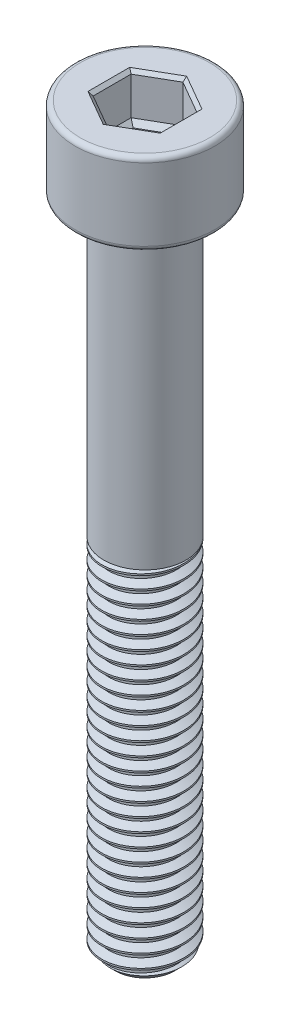
SolidWorks part; units mm, degrees
material "AISI Type A2 Tool Steel"
ref_plane "Front Plane" through (0, 0, 0) normal (0, 0, 1) x (1, 0, 0)
ref_plane "Top Plane" through (0, 0, 0) normal (0, 1, 0) x (1, 0, 0)
ref_plane "Right Plane" through (0, 0, 0) normal (1, 0, 0) x (0, 0, -1)
sketch "Sketch1" plane through (0, 0, 0) normal (0, 1, 0) x (1, 0, 0)
  circle A0 centre (0, 0) radius 2.5
  dimension "D1" = 5
extrude "Boss-Extrude1" add sketch "Sketch1" along normal blind 22
thread "Thread1" pitch 0.8 method cut profile "Thread Profile1" start angle 0, offset 1, length 0, pitch 0.8, diameter 5
ref_plane "Plane1" through (-2.5, 23, 0) normal (0, 0, 1) x (-1, 0, 0)
sketch "Thread Profile1" plane through (-2.5, 23, 0) normal (0, 0, 1) x (-1, 0, 0)
  line L0 (0, 0) -> (0, 0.8) construction
  line L11 (0, 0) -> (0, 0.7)
  line L12 (0, 0.7) -> (-0.433, 0.45)
  line L13 (-0.433, 0.45) -> (-0.433, 0.25)
  line L15 (-0.433, 0.25) -> (0, 0)
  line L17 (-0.433, 0.35) -> (0, 0.35) construction
  point P2 (0, 0)
  dimension "Pitch" = 0.8
  dimension "Profile_Angle" = 60
  dimension "Profile_Land" = 0.2
  dimension "Profile_Height" = 0.433
sketch "Sketch2" plane through (0, 22, 0) normal (0, 1, 0) x (1, 0, 0)
  circle A0 centre (0, 0) radius 2.5
  dimension "D1" = 5
extrude "Boss-Extrude2" add sketch "Sketch2" along normal blind 18
sketch "Sketch3" plane through (0, 40, 0) normal (0, 1, 0) x (1, 0, 0)
  circle A0 centre (0, 0) radius 4.25
  dimension "D1" = 8.5
extrude "Boss-Extrude3" add sketch "Sketch3" along normal blind 5
fillet "Fillet1" radius 0.3 2 edges at (0, 40, 4.25) (0, 45, 4.25)
sketch "Sketch4" plane through (0, 0, 0) normal (0, 0, 1) x (1, 0, 0)
  line L0 (0, 0) -> (0, 0.4416) construction
  line L1 (0, 0) -> (2.51, 0) construction
  line L2 (2.51, 0) -> (2.51, 0.7)
  line L3 (2.51, 0.7) -> (1.81, 0)
  line L4 (1.81, 0) -> (2.51, 0)
  dimension "D1" = 0.7
  dimension "D2" = 45
  dimension "D3" = 2.51
revolve "Cut-Revolve1" cut sketch "Sketch4" angle 360 about L0
sketch "Sketch5" plane through (0, 45, 0) normal (0, 1, 0) x (1, 0, 0)
  line L1 (0, 2.3094) -> (-2, 1.1547)
  line L2 (-2, 1.1547) -> (-2, -1.1547)
  line L3 (-2, -1.1547) -> (0, -2.3094)
  line L4 (0, -2.3094) -> (2, -1.1547)
  line L5 (2, -1.1547) -> (2, 1.1547)
  line L6 (2, 1.1547) -> (0, 2.3094)
  circle A0 centre (0, 0) radius 2 construction
  dimension "D1" = 4
extrude "Cut-Extrude1" cut sketch "Sketch5" against normal blind 2.5
chamfer "Chamfer1" distance 0.2 angle 45 6 edges at (-1, 45, 1.7321) (1, 45, 1.7321) (2, 45, 0) (1, 45, -1.7321) (-1, 45, -1.7321) (-2, 45, 0)
sketch "Sketch6" plane through (0, 42.5, 0) normal (0, 1, 0) x (1, 0, 0)
  line L1 (0, 2.3094) -> (-2, 1.1547)
  line L2 (-2, 1.1547) -> (-2, -1.1547)
  line L3 (-2, -1.1547) -> (0, -2.3094)
  line L4 (0, -2.3094) -> (2, -1.1547)
  line L5 (2, -1.1547) -> (2, 1.1547)
  line L6 (2, 1.1547) -> (0, 2.3094)
  circle A0 centre (0, 0) radius 2 construction
extrude "Cut-Extrude2" cut sketch "Sketch6" against normal blind 0.3 draft 45
